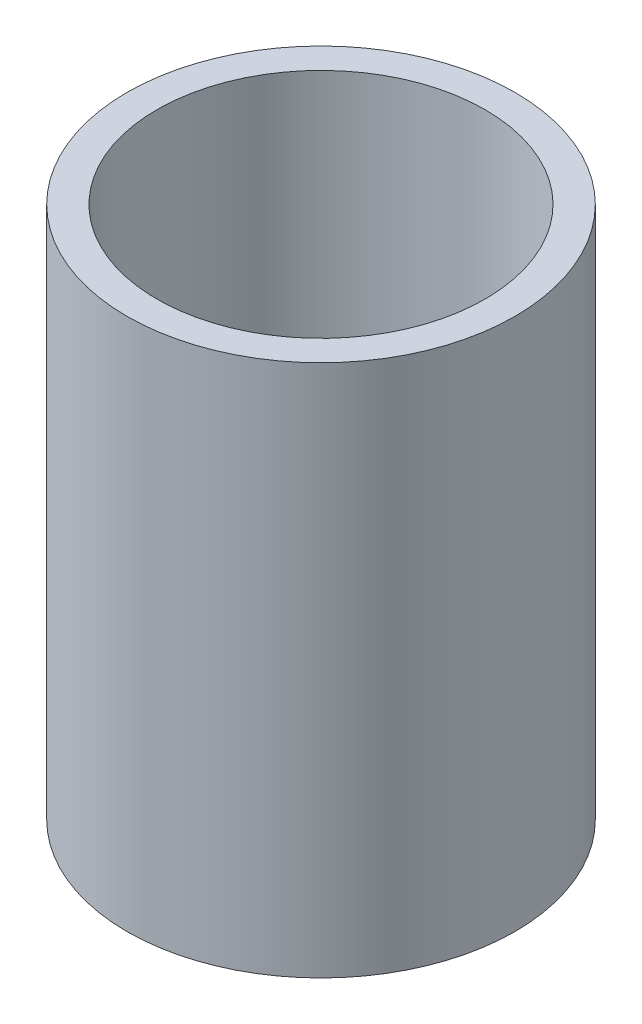
SolidWorks part; units mm, degrees
ref_plane "Front Plane" through (0, 0, 0) normal (0, 0, 1) x (1, 0, 0)
ref_plane "Top Plane" through (0, 0, 0) normal (0, 1, 0) x (1, 0, 0)
ref_plane "Right Plane" through (0, 0, 0) normal (1, 0, 0) x (0, 0, -1)
sketch "Sketch1" plane through (0, 0, 0) normal (0, 1, 0) x (1, 0, 0)
  circle A0 centre (0, 0) radius 57.5
  dimension "SLEEVE_OD" = 115
extrude "Boss-Extrude1" add sketch "Sketch1" along normal blind 157.9494
sketch "Sketch2" plane through (0, 0, 0) normal (0, 1, 0) x (1, 0, 0)
  circle A0 centre (0, 0) radius 48.6431
  dimension "BORE_D" = 97.2862
extrude "Cut-Extrude1" cut sketch "Sketch2" along normal through all
chamfer "Chamfer1" distance 3.5568 angle 60 rebuild error yes
